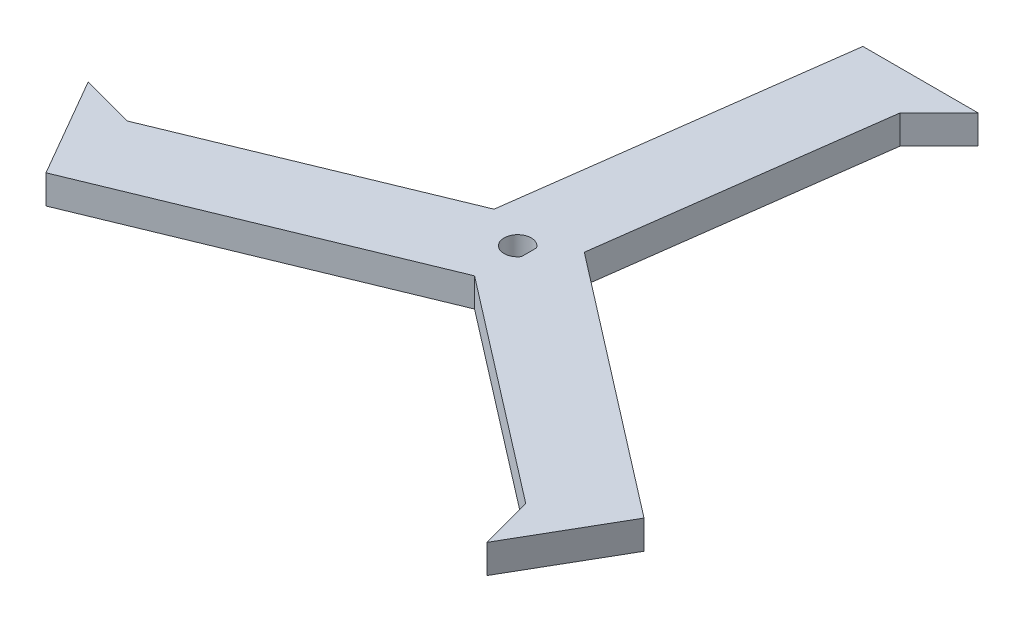
SolidWorks part; units mm, degrees
ref_plane "Front Plane" through (0, 0, 0) normal (0, 0, 1) x (1, 0, 0)
ref_plane "Top Plane" through (0, 0, 0) normal (0, 1, 0) x (1, 0, 0)
ref_plane "Right Plane" through (0, 0, 0) normal (1, 0, 0) x (0, 0, -1)
sketch "Sketch2" plane through (0, 0, 0) normal (0, 1, 0) x (1, 0, 0)
  line L0 (2.5, 1.6583) -> (2.5, -1.6583)
  line L1 (0, 76.2) -> (25.4, 76.2)
  line L2 (0, 0) -> (-8.9803, 8.9803) construction
  line L3 (0, 0) -> (8.9803, 8.9803) construction
  line L4 (0, 0) -> (0, 3) construction
  line L5 (-9.5937, 4.3884) -> (0, 76.2)
  line L6 (25.4, 76.2) -> (16.8134, 67.6134)
  line L7 (16.8134, 67.6134) -> (8.5974, 6.1142)
  line L8 (50.1482, -48.3675) -> (0.9963, -10.5026)
  line L9 (53.2911, -60.097) -> (50.1482, -48.3675)
  line L10 (65.9911, -38.1) -> (53.2911, -60.097)
  line L11 (8.5974, 6.1142) -> (65.9911, -38.1)
  line L12 (-66.9616, -19.2459) -> (-9.5937, 4.3884)
  line L13 (-78.6911, -16.103) -> (-66.9616, -19.2459)
  line L14 (-65.9911, -38.1) -> (-78.6911, -16.103)
  line L15 (0.9963, -10.5026) -> (-65.9911, -38.1)
  arc A0 (2.5, 1.6583) -> (2.5, -1.6583) centre (0, 0) ccw
  circle A1 centre (0, 0) radius 12.7 construction
  point P5 (3, 0)
  point P36 (0, 0)
  dimension "D1" = 6
  dimension "D6" = 25.4
  dimension "D2" = 0.5
  dimension "D3" = 76.2
  dimension "D4" = 90
  dimension "D5" = 25.4
  dimension "D7" = 45
  dimension "D8" = 45
  dimension "D9" = 3
extrude "Boss-Extrude1" add sketch "Sketch2" along normal blind 6.35 contours L12 L13 L14 L15 L8 L9 L10 L11 L7 L6 L1 L5 A0 region at (12.7, 0, -74.2123)
fillet "Fillet1" [suppressed] radius 2.54
